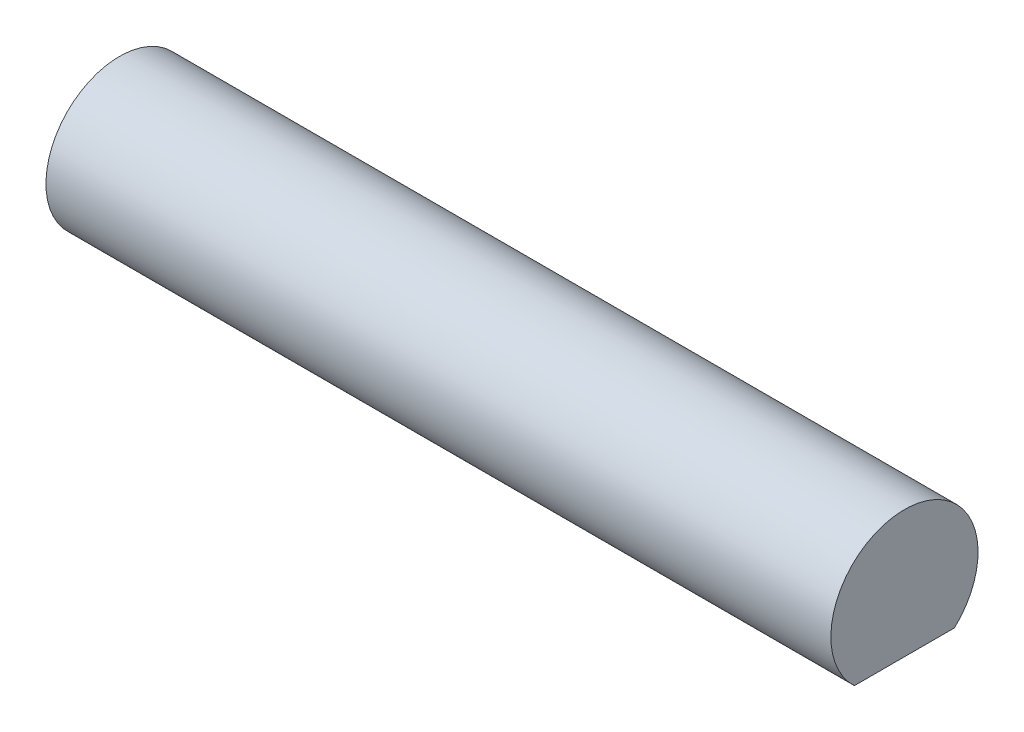
SolidWorks part; units mm, degrees
ref_plane "Front Plane" through (0, 0, 0) normal (0, 0, 1) x (1, 0, 0)
ref_plane "Top Plane" through (0, 0, 0) normal (0, 1, 0) x (1, 0, 0)
ref_plane "Right Plane" through (0, 0, 0) normal (1, 0, 0) x (0, 0, -1)
sketch "Sketch1" plane through (0, 0, 0) normal (1, 0, 0) x (0, 0, -1)
  line L0 (1.0198, -1.1) -> (-1.0198, -1.1)
  circle A0 centre (0, 0) radius 1.5
  dimension "D1" = 3
  dimension "D2" = 1.1
extrude "Boss-Extrude1" add sketch "Sketch1" along normal mid plane 16 contours L0 A0 region at (0, 0.1086, 0)
move or copy body "Body-Move/Copy1" [suppressed] bodies to move or copy 101
